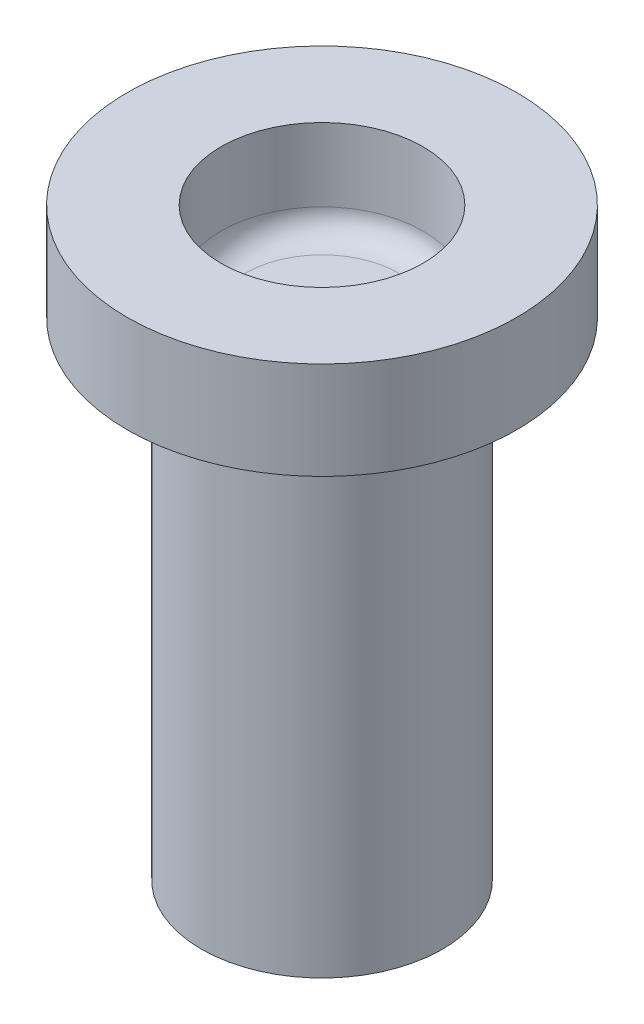
SolidWorks part; units mm, degrees
note: The reader was unsure of these and kept them because the rebuilt part matched: shared geometry of "Sketch1<2>".
ref_plane "Front Plane" through (0, 0, 0) normal (0, 0, 1) x (1, 0, 0)
ref_plane "Top Plane" through (0, 0, 0) normal (0, 1, 0) x (1, 0, 0)
ref_plane "Right Plane" through (0, 0, 0) normal (1, 0, 0) x (0, 0, -1)
sketch "Sketch1" plane through (0, 0, 0) normal (0, 1, 0) x (1, 0, 0)
  circle A1 centre (0, 0) radius 2.475
  circle A2 centre (0, 0) radius 1.5
  dimension "D1" = 4.95
  dimension "D2" = 3
extrude "Boss-Extrude1" add sketch "Sketch1" along normal blind 5
extrude "Boss-Extrude2" add sketch "Sketch1<2>" along normal blind 5 from surface at 5 contours A1 A2 | A2 starting at face at (0, 5, 2.475)
sketch "Sketch1<2>" plane through (0, 0, 0) normal (0, 1, 0) x (1, 0, 0) same geometry as "Sketch1"
sketch "Sketch2" plane through (0, 10, 0) normal (0, 1, 0) x (1, 0, 0)
  circle A1 centre (0, 0) radius 4
  circle A2 centre (0, 0) radius 2.075
  dimension "D1" = 4.15
  dimension "D2" = 8
extrude "Boss-Extrude3" add sketch "Sketch2" along normal blind 2
fillet "Fillet1" radius 0.5 2 edges at (0, 10, 2.075) (0, 10, 2.475)
